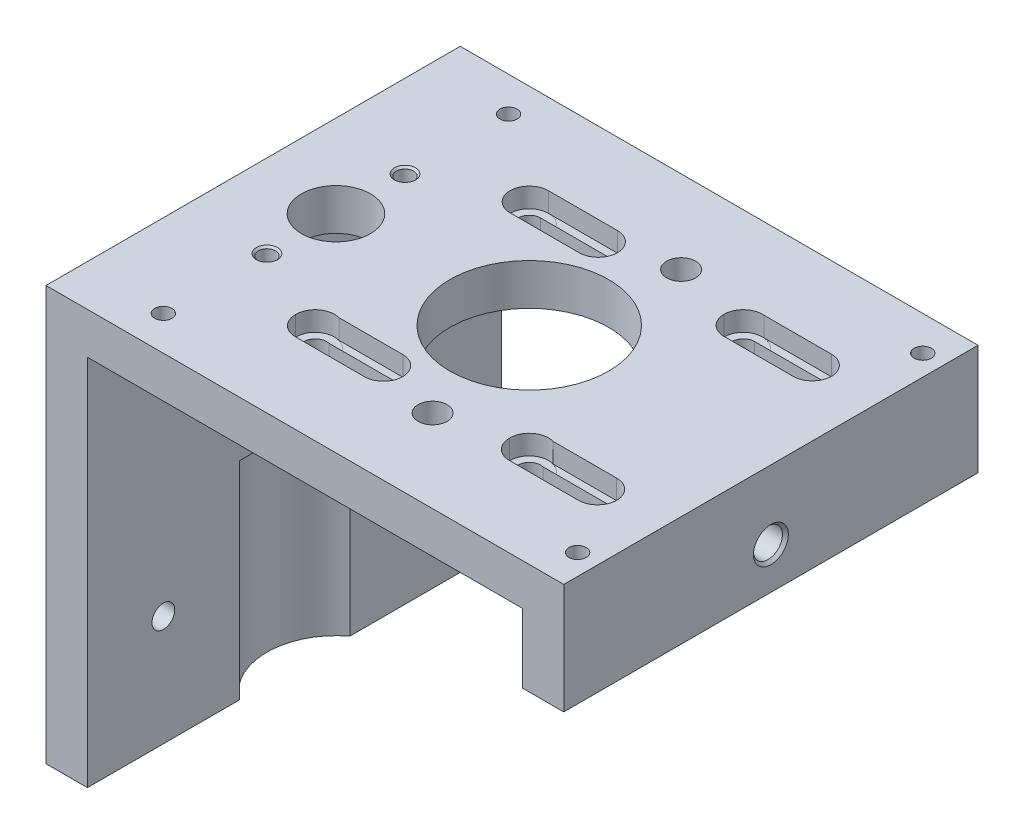
SolidWorks part; units mm, degrees
material "6061 Alloy"
ref_plane "Front Plane" through (0, 0, 0) normal (0, 0, 1) x (1, 0, 0)
ref_plane "Top Plane" through (0, 0, 0) normal (0, 1, 0) x (1, 0, 0)
ref_plane "Right Plane" through (0, 0, 0) normal (1, 0, 0) x (0, 0, -1)
sketch "Sketch1" plane through (0, 0, 0) normal (0, 0, 1) x (1, 0, 0)
  line L0 (0, 0) -> (6, 0)
  line L1 (69, 54) -> (69, 44)
  line L2 (0, 0) -> (0, 60)
  line L3 (0, 60) -> (75, 60)
  line L4 (75, 44) -> (75, 60)
  line L5 (69, 44) -> (75, 44)
  line L6 (6, 0) -> (6, 54)
  line L7 (6, 54) -> (69, 54)
  dimension "D1" = 75
  dimension "D2" = 6
  dimension "D3" = 6
  dimension "D4" = 60
  dimension "D5" = 10
  dimension "D6" = 6
extrude "Boss-Extrude1" add sketch "Sketch1" along normal blind 60
sketch "Sketch2" plane through (0, 60, 0) normal (0, 1, 0) x (1, 0, 0)
  line L0 (24.5, -45.5) -> (55.5, -45.5) construction
  line L1 (24.5, -45.5) -> (24.5, -14.5) construction
  line L3 (0, -60) -> (0, 0) construction
  line L4 (75, -30) -> (0, -30) construction
  line L5 (75, -60) -> (75, 0) construction
  circle A0 centre (40, -30) radius 11.5
  point P2 (24.5, -45.5)
  point P3 (40, -45.5)
  point P4 (24.5, -30)
  point P5 (55.5, -45.5)
  point P6 (24.5, -14.5)
  point P7 (55.5, -14.5)
  dimension "D1" = 23
  dimension "D2" = 31
  dimension "D3" = 31
  dimension "D7" = 40
  dimension "D4" = 2
  dimension "D5" = 2
extrude "Cut-Extrude1" cut sketch "Sketch2" against normal through all
ref_axis "Axis1" through (40, 54, 30) along (0, 1, 0)
hole_wizard "CBORE for #4 Socket Head Cap Screw1" positions "Sketch7" profile "Sketch6" counterbore size "#4" standard "Ansi Inch" end condition through all
sketch "Sketch7" plane through (0, 60, 0) normal (0, 1, 0) x (-1, 0, 0)
  line L0 (-24.5, 45.5) -> (-55.5, 45.5) construction
  line L1 (-24.5, 45.5) -> (-24.5, 14.5) construction
  point P0 (-24.5, 45.5)
  point P8 (-55.5, 45.5)
  point P9 (-24.5, 14.5)
  point P10 (-55.5, 14.5)
  point P34 (-40, 45.5)
  point P35 (-24.5, 30)
  dimension "D1" = 31
  dimension "D4" = 31
  dimension "D2" = 2
  dimension "D3" = 2
sketch "Sketch6" plane through (24.5, 60, 45.5) normal (1, 0, 0) x (0, 0, 1)
  line L0 (0, 0) -> (0, 60)
  line L1 (0, 60) -> (1.6319, 60)
  line L3 (1.6319, 60) -> (1.632, 2.8448)
  line L4 (1.632, 2.8448) -> (2.7788, 2.8448)
  line L5 (2.7788, 2.8448) -> (2.7788, 0)
  line L7 (2.7788, 0) -> (0, 0)
  line L11 (0, -6.35) -> (0, 107.95) construction
  dimension "Thru Hole Dia." = 3.2639
  dimension "Thru Hole Depth" = 60
  dimension "C'Bore Dia." = 5.5575
  dimension "C'Bore Depth" = 2.8448
sketch "Sketch24" plane through (0, 60, 0) normal (0, 1, 0) x (1, 0, 0)
  line L0 (24.5, -14.5) -> (34.5, -14.5) construction
  line L1 (24.5, -12.868) -> (34.5, -12.868)
  line L2 (24.5, -16.132) -> (34.5, -16.132)
  line L3 (65.5138, -30) -> (17.4578, -30) construction
  line L4 (55.5, -14.5) -> (65.5, -14.5) construction
  line L5 (55.5, -12.868) -> (65.5, -12.868)
  line L6 (55.5, -16.132) -> (65.5, -16.132)
  line L7 (24.5, -45.543) -> (34.5, -45.543) construction
  line L8 (24.5, -43.911) -> (34.5, -43.911)
  line L9 (24.5, -47.1749) -> (34.5, -47.1749)
  line L10 (55.5, -45.543) -> (65.5, -45.543) construction
  line L11 (55.5, -43.911) -> (65.5, -43.911)
  line L12 (55.5, -47.1749) -> (65.5, -47.1749)
  line L13 (40, -9.8721) -> (40, -50.1279) construction
  arc A0 (24.5, -12.868) -> (24.5, -16.132) centre (24.5, -14.5) ccw
  arc A1 (34.5, -16.132) -> (34.5, -12.868) centre (34.5, -14.5) ccw
  circle A2 centre (24.5, -14.5) radius 1.632 construction
  arc A3 (55.5, -12.868) -> (55.5, -16.132) centre (55.5, -14.5) ccw
  arc A4 (65.5, -16.132) -> (65.5, -12.868) centre (65.5, -14.5) ccw
  arc A5 (24.5, -43.911) -> (24.5, -47.1749) centre (24.5, -45.543) ccw
  arc A6 (34.5, -47.1749) -> (34.5, -43.911) centre (34.5, -45.543) ccw
  arc A7 (55.5, -43.911) -> (55.5, -47.1749) centre (55.5, -45.543) ccw
  arc A8 (65.5, -47.1749) -> (65.5, -43.911) centre (65.5, -45.543) ccw
  point P3 (29.5, -14.5)
  point P18 (60.5, -14.5)
  point P25 (29.5, -45.543)
  point P32 (60.5, -45.543)
  dimension "D1" = 10
  dimension "D2" = 2
  dimension "D3" = 2
extrude "Cut-Extrude5" cut sketch "Sketch24" against normal up to next
sketch "Sketch25" plane through (0, 60, 0) normal (0, 1, 0) x (1, 0, 0)
  line L0 (24.5, -14.5) -> (34.5, -14.5) construction
  line L1 (24.5, -11.7212) -> (34.5, -11.7212)
  line L2 (24.5, -17.2788) -> (34.5, -17.2788)
  line L3 (55.5, -14.5099) -> (65.5, -14.5099) construction
  line L4 (55.5, -11.7311) -> (65.5, -11.7311)
  line L5 (55.5, -17.2886) -> (65.5, -17.2886)
  line L6 (24.5, -45.6008) -> (34.5, -45.6008) construction
  line L7 (24.5, -42.8221) -> (34.5, -42.8221)
  line L8 (24.5, -48.3796) -> (34.5, -48.3796)
  line L9 (55.5, -45.6107) -> (65.5, -45.6107) construction
  line L10 (55.5, -42.832) -> (65.5, -42.832)
  line L11 (55.5, -48.3895) -> (65.5, -48.3895)
  arc A0 (24.5, -11.7212) -> (24.5, -17.2788) centre (24.5, -14.5) ccw
  arc A1 (34.5, -17.2788) -> (34.5, -11.7212) centre (34.5, -14.5) ccw
  arc A2 (26.7491, -12.868) -> (26.7491, -16.132) centre (24.5, -14.5) ccw construction
  arc A3 (55.5, -11.7311) -> (55.5, -17.2886) centre (55.5, -14.5099) ccw
  arc A4 (65.5, -17.2886) -> (65.5, -11.7311) centre (65.5, -14.5099) ccw
  arc A5 (24.5, -42.8221) -> (24.5, -48.3796) centre (24.5, -45.6008) ccw
  arc A6 (34.5, -48.3796) -> (34.5, -42.8221) centre (34.5, -45.6008) ccw
  arc A7 (55.5, -42.832) -> (55.5, -48.3895) centre (55.5, -45.6107) ccw
  arc A8 (65.5, -48.3895) -> (65.5, -42.832) centre (65.5, -45.6107) ccw
  point P4 (29.5, -14.5)
  point P17 (60.5, -14.5099)
  point P24 (29.5, -45.6008)
  point P31 (60.5, -45.6107)
  dimension "D1" = 10
  dimension "D2" = 2
  dimension "D3" = 2
extrude "Cut-Extrude6" cut sketch "Sketch25" against normal blind 2.84
hole_wizard "M3 Tapped Hole1" positions "Sketch9" profile "Sketch10" tap size "M3" standard "ISO"
sketch "Sketch9" plane through (0, 60, 0) normal (0, 1, 0) x (-1, 0, 0)
  line L0 (-12, 55) -> (-72, 55) construction
  line L1 (-12, 55) -> (-12, 5) construction
  line L20 (-75, 60) -> (0, 60) construction
  line L21 (0, 60) -> (0, 0) construction
  point P1 (-12, 55)
  point P5 (-72, 55)
  point P6 (-12, 5)
  point P7 (-72, 5)
  dimension "D1" = 60
  dimension "D2" = 50
  dimension "D6" = 5
  dimension "D7" = 12
  dimension "D3" = 2
  dimension "D4" = 2
sketch "Sketch10" plane through (12, 60, 55) normal (1, 0, 0) x (0, 0, 1)
  line L0 (0, 0) -> (0, 9.2511)
  line L1 (0, 9.2511) -> (1.25, 8.5)
  line L2 (1.25, 8.5) -> (1.25, 0)
  line L5 (1.25, 0) -> (0, 0)
  line L10 (0, 9.2511) -> (-1.25, 8.5) construction
  line L11 (0, -6.35) -> (0, 107.95) construction
  dimension "Tap Drill Dia." = 2.5
  dimension "Tap Drill Depth" = 8.5
  dimension "Drill Angle" = 118
cosmetic thread "Hole Thread1" parameters "D1"=6, "D2"=3
cosmetic thread "Hole Thread2" parameters "D1"=6, "D2"=3
cosmetic thread "Hole Thread3" parameters "D1"=6, "D2"=3
cosmetic thread "Hole Thread4" parameters "D1"=6, "D2"=3
hole_wizard "M5 Tapped Hole1" positions "Sketch14" profile "Sketch15" tap size "M5" standard "ISO" end condition through all
sketch "Sketch14" plane through (0, 60, 0) normal (0, 1, 0) x (-1, 0, 0)
  line L0 (-44, 12) -> (-44, 48) construction
  point P0 (-44, 12)
  point P1 (-44, 48)
  dimension "D1" = 18
  dimension "D2" = 18
  dimension "D3" = 4
sketch "Sketch15" plane through (44, 60, 12) normal (1, 0, 0) x (0, 0, 1)
  line L0 (0, 0) -> (0, 60)
  line L1 (0, 60) -> (2.1, 60)
  line L2 (2.1, 60) -> (2.1, 0)
  line L5 (2.1, 0) -> (0, 0)
  line L11 (0, -6.35) -> (0, 107.95) construction
  dimension "Thru Tap Drill Dia." = 4.2
  dimension "Thru Tap Drill Depth" = 60
cosmetic thread "Hole Thread5" parameters "D2"=5
cosmetic thread "Hole Thread6" parameters "D2"=5
sketch "Sketch11" plane through (0, 60, 0) normal (0, 1, 0) x (1, 0, 0)
  line L1 (0, -60) -> (0, 0) construction
  line L2 (75, -30) -> (0, -30) construction
  line L3 (75, -60) -> (75, 0) construction
  circle A0 centre (12, -30) radius 5
  dimension "D2" = 10
  dimension "D1" = 12
extrude "Cut-Extrude2" cut sketch "Sketch11" against normal through all
ref_axis "Axis2" through (12, 54, 30) along (0, 1, 0)
hole_wizard "M4 Tapped Hole1" positions "Sketch20" profile "Sketch19" tap size "M4" standard "ISO" end condition up to next
sketch "Sketch20" plane through (0, 0, 0) normal (-1, 0, 0) x (0, 0, 1)
  line L0 (30, 60) -> (30, 0) construction
  line L1 (60, 60) -> (0, 60) construction
  line L2 (60, 0) -> (0, 0) construction
  point P0 (11, 46)
  point P13 (11, 16)
  point P16 (49, 46)
  point P18 (49, 16)
  dimension "D1" = 14
  dimension "D2" = 30
  dimension "D3" = 38
cosmetic thread "Hole Thread7" parameters "D2"=4
cosmetic thread "Hole Thread8" parameters "D2"=4
cosmetic thread "Hole Thread9" parameters "D2"=4
cosmetic thread "Hole Thread10" parameters "D2"=4
sketch "Sketch19" plane through (0, 46, 11) normal (0, 1, 0) x (0, 0, 1)
  line L0 (0, 0) -> (0, 6)
  line L1 (0, 6) -> (1.65, 6)
  line L2 (1.65, 6) -> (1.65, 0.6)
  line L3 (1.65, 0.6) -> (2.25, 0)
  line L5 (2.25, 0) -> (0, 0)
  line L6 (-1.65, 0.6) -> (-2.25, 0) construction
  line L11 (0, -6.35) -> (0, 107.95) construction
  dimension "Thru Tap Drill Dia." = 3.3
  dimension "Thru Tap Drill Depth" = 6
  dimension "Near C'Sink Dia." = 4.5
  dimension "Near C'Sink Angle" = 90
hole_wizard "M5 Tapped Hole2" positions "Sketch23" profile "Sketch22" tap size "M5" standard "ISO" end condition up to next
sketch "Sketch23" plane through (75, 0, 0) normal (1, 0, 0) x (0, 0, -1)
  line L0 (-30, 54) -> (-30, 60) construction
  line L1 (-60, 60) -> (0, 60) construction
  point P0 (-30, 50)
  dimension "D1" = 10
cosmetic thread "Hole Thread11" parameters "D2"=5
sketch "Sketch22" plane through (75, 50, 30) normal (0, 1, 0) x (0, 0, -1)
  line L0 (0, 0) -> (0, 6)
  line L1 (0, 6) -> (2.1, 6)
  line L2 (2.1, 6) -> (2.1, 0.425)
  line L3 (2.1, 0.425) -> (2.525, 0)
  line L5 (2.525, 0) -> (0, 0)
  line L6 (-2.1, 0.425) -> (-2.525, 0) construction
  line L11 (0, -6.35) -> (0, 107.95) construction
  dimension "Thru Tap Drill Dia." = 4.2
  dimension "Thru Tap Drill Depth" = 6
  dimension "Near C'Sink Dia." = 5.05
  dimension "Near C'Sink Angle" = 90
sketch "Sketch16" plane through (0, 0, 0) normal (0, -1, 0) x (1, 0, 0)
  circle A0 centre (12, 30) radius 10
extrude "Cut-Extrude4" cut sketch "Sketch16" against normal blind 30
hole_wizard "M3 Tapped Hole2" positions "Sketch28" profile "Sketch29" tap size "M3" standard "ISO" end condition up to next
sketch "Sketch28" plane through (0, 54, 0) normal (0, -1, 0) x (1, 0, 0)
  line L0 (12, 43.3514) -> (12, 16.6486) construction
  line L2 (20.0951, 30) -> (3.9049, 30) construction
  point P12 (12, 40)
  point P26 (12, 20)
  dimension "D1" = 20
cosmetic thread "Hole Thread12" parameters "D2"=3
cosmetic thread "Hole Thread13" parameters "D2"=3
sketch "Sketch29" plane through (12, 54, 40) normal (1, 0, 0) x (0, 0, -1)
  line L0 (0, 0) -> (0, 6)
  line L1 (0, 6) -> (1.525, 6)
  line L2 (1.25, 5.725) -> (1.25, 0.275)
  line L3 (1.25, 0.275) -> (1.525, 0)
  line L5 (1.525, 0) -> (0, 0)
  line L6 (-1.25, 0.275) -> (-1.525, 0) construction
  line L7 (1.525, 6) -> (1.25, 5.725)
  line L8 (-1.525, 6) -> (-1.25, 5.725) construction
  line L11 (0, -6.35) -> (0, 107.95) construction
  dimension "Thru Tap Drill Dia." = 2.5
  dimension "Thru Tap Drill Depth" = 6
  dimension "Near C'Sink Dia." = 3.05
  dimension "Near C'Sink Angle" = 90
  dimension "Far C'Sink Dia." = 3.05
  dimension "Far C'Sink Angle" = 90
